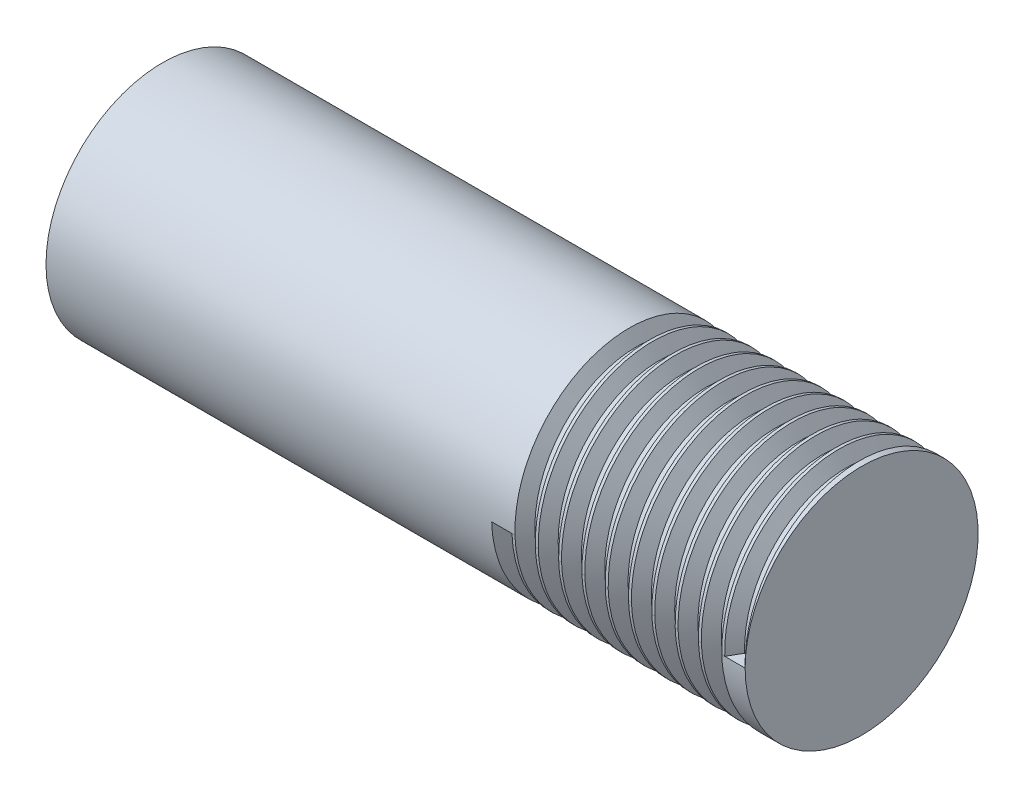
SolidWorks part; units mm, degrees
ref_plane "Front Plane" through (0, 0, 0) normal (0, 0, 1) x (1, 0, 0)
ref_plane "Top Plane" through (0, 0, 0) normal (0, 1, 0) x (1, 0, 0)
ref_plane "Right Plane" through (0, 0, 0) normal (1, 0, 0) x (0, 0, -1)
sketch "Sketch1" plane through (0, 0, 0) normal (1, 0, 0) x (0, 0, -1)
  circle A0 centre (0, 0) radius 5
extrude "Boss-Extrude1" add sketch "Sketch1" along normal blind 30
thread "Thread1" pitch 1 method cut profile "Thread Profile1" start angle 0, offset 0, length 10, pitch 1, diameter 10
ref_plane "Plane1" through (30, 0, 5) normal (0, -1, 0) x (0, 0, 1)
sketch "Thread Profile1" plane through (30, 0, 5) normal (0, -1, 0) x (0, 0, 1)
  line L0 (0, 0) -> (0, 1) construction
  line L11 (0, 0) -> (0, 0.875)
  line L12 (0, 0.875) -> (-0.5413, 0.5625)
  line L13 (-0.5413, 0.5625) -> (-0.5413, 0.3125)
  line L15 (-0.5413, 0.3125) -> (0, 0)
  line L17 (-0.5413, 0.4375) -> (0, 0.4375) construction
  point P2 (0, 0)
  dimension "Pitch" = 1
  dimension "Profile_Angle" = 60
  dimension "Profile_Land" = 0.25
  dimension "Profile_Height" = 0.5413
